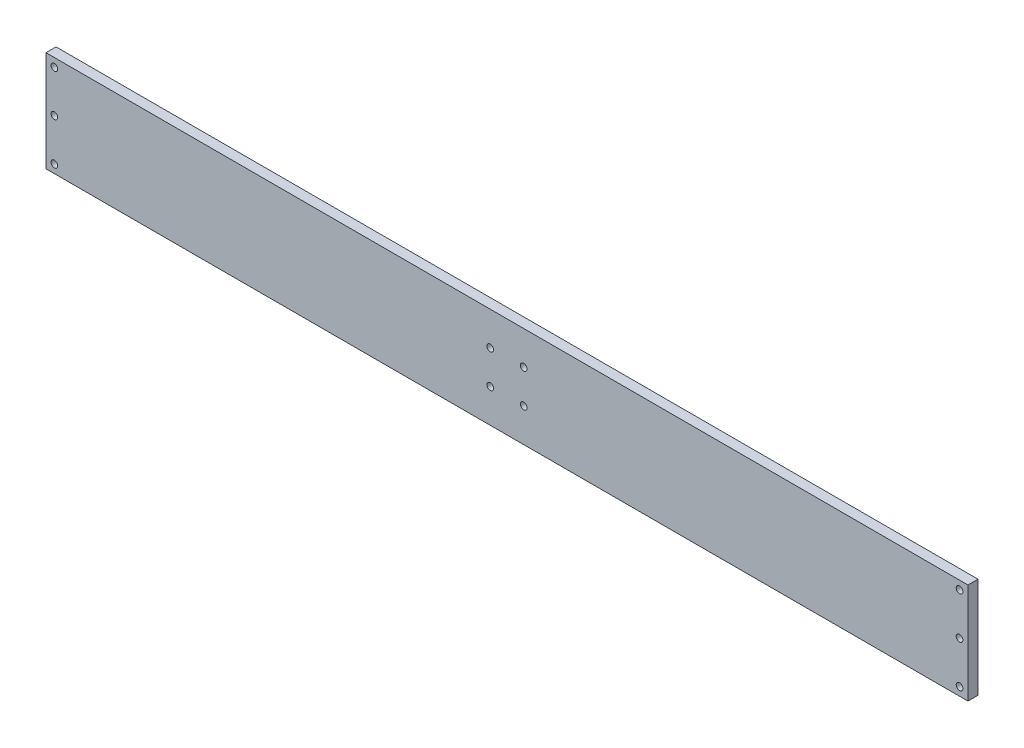
SolidWorks part; units mm, degrees
ref_plane "Piano frontale" through (0, 0, 0) normal (0, 0, 1) x (1, 0, 0)
ref_plane "Piano superiore" through (0, 0, 0) normal (0, 1, 0) x (1, 0, 0)
ref_plane "Piano destro" through (0, 0, 0) normal (1, 0, 0) x (0, 0, -1)
sketch "Schizzo1" plane through (0, 0, 0) normal (0, 0, 1) x (1, 0, 0)
  line L0 (5, 60) -> (5, 0) construction
  line L1 (0, 0) -> (550, 0)
  line L2 (0, 0) -> (0, 60)
  line L3 (0, 60) -> (550, 60)
  line L4 (550, 0) -> (550, 60)
  line L5 (0, 30) -> (10.4526, 30) construction
  line L6 (275, 60) -> (275, 0) construction
  circle A0 centre (5, 30) radius 2
  circle A1 centre (5, 55) radius 2
  circle A2 centre (5, 5) radius 2
  circle A3 centre (545, 5) radius 2
  circle A4 centre (545, 55) radius 2
  circle A5 centre (545, 30) radius 2
  dimension "D4" = 4
  dimension "D5" = 5
  dimension "D1" = 60
  dimension "D2" = 550
  dimension "D3" = 25
extrude "Estrusione-Estrusione1" add sketch "Schizzo1" against normal blind 6
sketch "Schizzo2" plane through (0, 0, 0) normal (0, 0, 1) x (1, 0, 0)
  line L0 (275, 60) -> (275, 0) construction
  line L1 (550, 60) -> (0, 60) construction
  line L2 (0, 30) -> (550, 30) construction
  line L3 (0, 0) -> (550, 0) construction
  line L4 (285, 30) -> (265, 30) construction
  line L9 (0, 60) -> (0, 0) construction
  line L10 (550, 0) -> (550, 60) construction
  circle A0 centre (265, 40) radius 2
  circle A1 centre (285, 40) radius 2
  circle A4 centre (285, 20) radius 2
  circle A5 centre (265, 20) radius 2
  dimension "D3" = 4
  dimension "D1" = 10
  dimension "D2" = 10
  dimension "D4" = 10
extrude "Taglio-Estrusione1" cut sketch "Schizzo2" against normal through all
